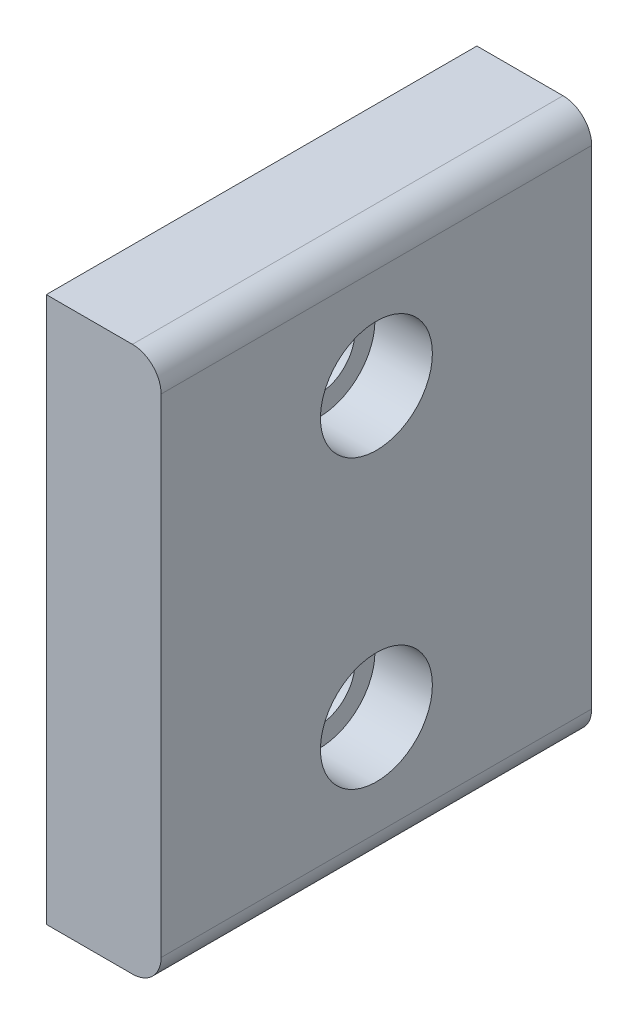
SolidWorks part; units mm, degrees
ref_plane "Спереди" through (0, 0, 0) normal (0, 0, 1) x (1, 0, 0)
ref_plane "Сверху" through (0, 0, 0) normal (0, 1, 0) x (1, 0, 0)
ref_plane "Справа" through (0, 0, 0) normal (1, 0, 0) x (0, 0, -1)
sketch "Эскиз1" plane through (0, 0, 0) normal (1, 0, 0) x (0, 0, -1)
  line L0 (-7.5, 0) -> (7.5, 0) construction
  line L1 (-7.5, 9.5) -> (7.5, 9.5)
  line L2 (-7.5, 9.5) -> (-7.5, -9.5)
  line L3 (-7.5, -9.5) -> (7.5, -9.5)
  line L4 (7.5, 9.5) -> (7.5, -9.5)
  line L5 (-7.5, 9.5) -> (7.5, -9.5) construction
  line L6 (-7.5, -9.5) -> (7.5, 9.5) construction
  circle A0 centre (0, 5) radius 1.25
  circle A1 centre (0, -5) radius 1.25
  point P0 (0, 0)
  dimension "D4" = 2.5
  dimension "D1" = 19
  dimension "D2" = 15
  dimension "D3" = 10
extrude "Бобышка-Вытянуть1" add sketch "Эскиз1" along normal blind 4
sketch "Эскиз2" plane through (4, 0, 0) normal (1, 0, 0) x (0, 0, -1)
  circle A0 centre (0, 5) radius 1.95
  circle A1 centre (0, -5) radius 1.95
  dimension "D1" = 3.9
  dimension "D2" = 3.9
extrude "Вырез-Вытянуть1" cut sketch "Эскиз2" against normal blind 2
fillet "Скругление1" radius 1 2 edges at (4, -9.5, 0) (4, 9.5, 0)
equation "\"motor_diameter\"= 30"
equation "\"mm_diameter\"= IIF ( \"motor_diameter\" < 34 , 41 , \"motor_diameter\" + 8 )"
equation "\"upper_shafts_diameter\"= 5"
equation "\"upper_shats_length\"= 180"
equation "\"upper_bearing_d1\"= 10"
equation "\"upper_bearing_d2\"= 5"
equation "\"upper_bearing_h\"= 15"
equation "\"lower_shafts_diameter\"= 5"
equation "\"lower_shafts_length\"= 180"
equation "\"lower_bearing_d1\"= 10"
equation "\"lower_bearing_d2\"= 5"
equation "\"lower_bearing_h\"= 15"
equation "\"print_offset\"= 0.5"
equation "\"bh_screws_d\"= 2"
equation "\"bh_screws_h\"= 20"
equation "\"bh_screws_hh_d\"= 3.4"
equation "\"bh_screws_hh_h\"= 2"
equation "\"bh_nut_d\"= 3.8"
equation "\"bh_nut_h\"= 2"
equation "\"motor_screws_d\"= 3"
equation "\"motor_screws_h\"= 16"
equation "\"motor_screws_hh_d\"= 5.5"
equation "\"motor_screws_hh_h\"= 3"
equation "\"plate_hole_distance\"= 25.4"
equation "\"plate_screws_d\"= 6.5"
equation "\"shafts_diameter\"= IIF ( \"mm_diameter\" < 42 , 42 + 8 , \"mm_diameter\" + 8 )"
equation "\"central_hole_diameter\"= 8"
equation "\"bh_thikness\"= 4"
equation "\"ends_screws_d\"= 4"
equation "\"ends_screws_h\"= 16"
equation "\"ends_screws_hh_d\"= 6.7"
equation "\"ends_screws_hh_h\"= 4.1"
equation "\"ends_nut_d\"= 6.8"
equation "\"ends_nut_h\"= 3"
equation "\"system_radius\" = ( \"shafts_diameter\" + 12 + \"bh_thikness\" / 2 ) / 2"
equation "\"encoder_distance\"= \"system_radius\" + 4"
equation "\"tape_position\"= \"encoder_distance\" - 2 + 3.9 + 1.7 / 2"
equation "\"D1@Эскиз1\"=\"upper_bearing_h\" + 6 + 3 - 8 + 3"
equation "\"D4@Эскиз1\"=\"bh_screws_d\"+\"print_offset\""
equation "\"D1@Эскиз2\"=\"bh_screws_hh_d\"+\"print_offset\""
equation "\"D2@Эскиз2\"=\"D1@Эскиз2\""
